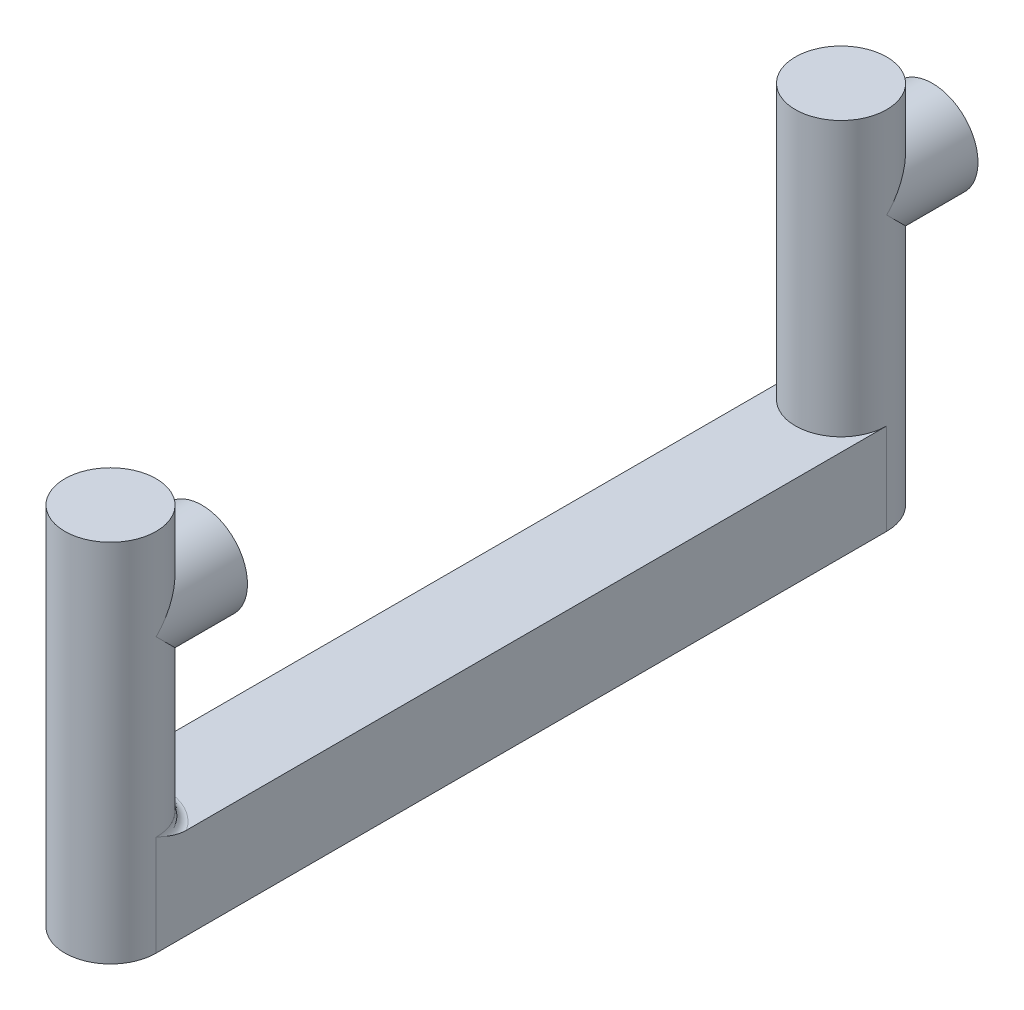
SolidWorks part; units mm, degrees
ref_plane "Front Plane" through (0, 0, 0) normal (0, 0, 1) x (1, 0, 0)
ref_plane "Top Plane" through (0, 0, 0) normal (0, 1, 0) x (1, 0, 0)
ref_plane "Right Plane" through (0, 0, 0) normal (1, 0, 0) x (0, 0, -1)
sketch "Sketch1" plane through (0, 0, 0) normal (0, 1, 0) x (1, 0, 0)
  line L1 (-2.5, 20) -> (2.5, 20)
  line L2 (-2.5, 20) -> (-2.5, 0)
  line L3 (-2.5, 0) -> (2.5, 0)
  line L4 (2.5, 20) -> (2.5, 0)
  dimension "D1" = 5
  dimension "D2" = 20
extrude "Boss-Extrude1" add sketch "Sketch1" along normal blind 5
sketch "Sketch4" plane through (0, 0, 0) normal (0, 1, 0) x (1, 0, 0)
  line L0 (-2.5, 0) -> (2.5, 0) construction
  circle A0 centre (0, 0) radius 2.5
  dimension "D1" = 5
extrude "Boss-Extrude2" add sketch "Sketch4" along normal blind 20
fillet "Fillet1" radius 0.5 1 edges at (0, 5, -2.5)
mirror "Mirror1" about plane through (-2.5, 5, -20) normal (0, 0, 1) of "Boss-Extrude2", "Boss-Extrude1"
sketch "Sketch5" plane through (0, 0, 0) normal (0, 0, 1) x (1, 0, 0)
  line L0 (0, 0) -> (0, 20) construction
  line L1 (2.5, 20) -> (-2.5, 20) construction
  circle A0 centre (0, 15) radius 2.5
  point P7 (0, 0)
  dimension "D1" = 5
  dimension "D2" = 5
extrude "Boss-Extrude3" add sketch "Sketch5" against normal blind 5
extrude "Boss-Extrude4" add sketch "Sketch5<2>" against normal blind 5 from offset 40 offset against normal yes
sketch "Sketch5<2>" plane through (0, 0, 0) normal (0, 0, 1) x (1, 0, 0) same geometry as "Sketch5"
